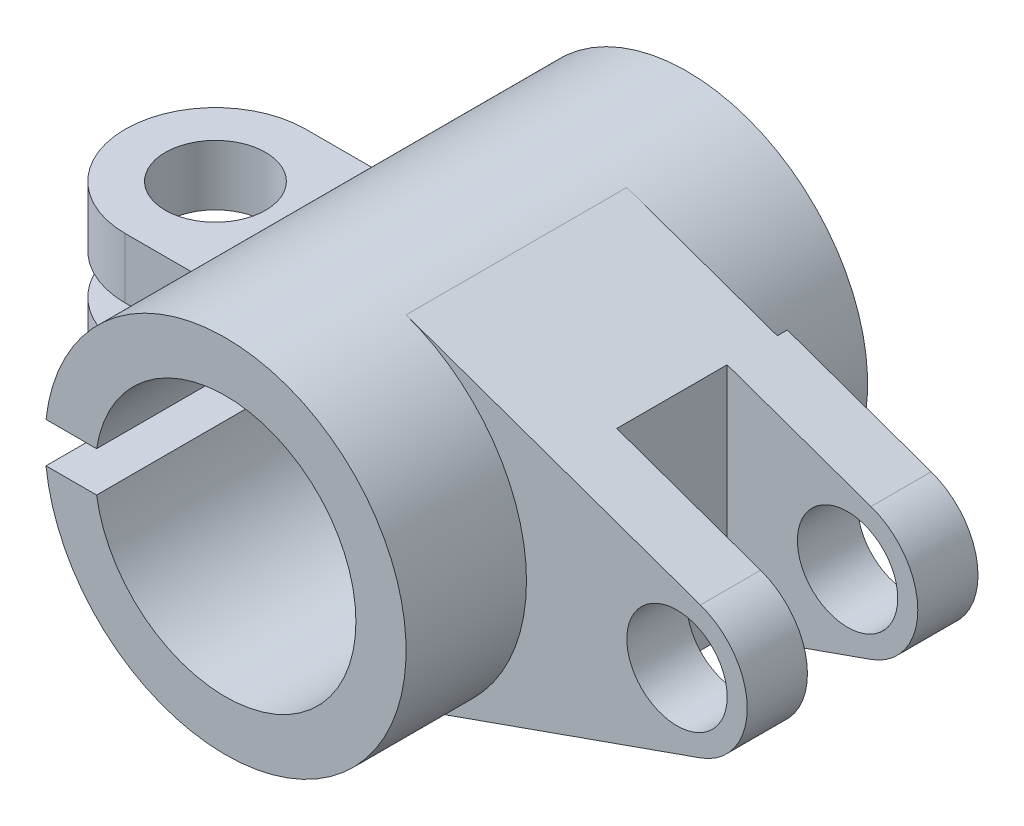
SolidWorks part; units mm, degrees
ref_plane "Front Plane" through (0, 0, 0) normal (0, 0, 1) x (1, 0, 0)
ref_plane "Top Plane" through (0, 0, 0) normal (0, 1, 0) x (1, 0, 0)
ref_plane "Right Plane" through (0, 0, 0) normal (1, 0, 0) x (0, 0, -1)
sketch "Sketch1" plane through (0, 0, 0) normal (0, 0, 1) x (1, 0, 0)
  line L0 (-16.1245, 8) -> (-33, 8)
  line L1 (-33, 8) -> (-33, 2)
  line L2 (0, 0) -> (-50000, 0) construction
  line L3 (0, 0) -> (0, -50000) construction
  line L4 (-33, 2) -> (-12.8452, 2)
  line L5 (-33, -8) -> (-33, -2)
  line L6 (-16.1245, -8) -> (-33, -8)
  line L7 (-33, -2) -> (-12.8452, -2)
  line L8 (6, 16.9706) -> (35.3333, 6.5997)
  line L9 (6, -16.9706) -> (35.3333, -6.5997)
  line L10 (21, 11.6673) -> (21, -11.6673)
  arc A0 (-12.8452, -2) -> (-12.8452, 2) centre (0, 0) ccw
  arc A1 (-17.8885, -2) -> (-17.8885, 2) centre (0, 0) ccw
  circle A2 centre (33, 0) radius 5
  arc A3 (35.3333, -6.5997) -> (35.3333, 6.5997) centre (33, 0) ccw
  dimension "D1" = 26
  dimension "D2" = 36
  dimension "D6" = 10
  dimension "D7" = 14
  dimension "D8" = 12
  dimension "D3" = 6
  dimension "D4" = 4
  dimension "D5" = 33
  dimension "D9" = 33
extrude "Boss-Extrude1" add sketch "Sketch1" along normal mid plane 46 contours A1 L4 A0 L7 region at (-6.5724, 16.2099, 0)
extrude "Boss-Extrude2" add sketch "Sketch1<3>" along normal mid plane 22 contours A1 L9 L10 L8 region at (13.3763, 13.9691, 0)
sketch "Sketch1<3>" plane through (0, 0, 0) normal (0, 0, 1) x (1, 0, 0) same geometry as "Sketch1"
extrude "Boss-Extrude3" add sketch "Sketch1<4>" along normal blind 6 from offset 5 contours L9 A3 L8 L10 A2 region at (27.5339, 0, 0)
sketch "Sketch1<4>" plane through (0, 0, 0) normal (0, 0, 1) x (1, 0, 0) same geometry as "Sketch1"
extrude "Boss-Extrude4" add sketch "Sketch1<5>" against normal blind 6 from offset 6 contours L9 A3 L8 L10 A2 region at (27.5339, 0, 0) offset against normal yes
sketch "Sketch1<5>" plane through (0, 0, 0) normal (0, 0, 1) x (1, 0, 0) same geometry as "Sketch1"
extrude "Boss-Extrude5" add sketch "Sketch1<6>" along normal mid plane 18 contours A1 L0 L1 L4 | A1 L7 L5 L6 region at (-25.0902, 5.0554, 0) region at (-25.0902, -5.0554, 0)
sketch "Sketch1<6>" plane through (0, 0, 0) normal (0, 0, 1) x (1, 0, 0) same geometry as "Sketch1"
fillet "Fillet1" 2 edges at (-33, 5, -9) (-33, 5, 9) type full round first side face at (-25.0689, 5.0193, -9) second side face at (-25.0689, 5.0193, 9) middle face at (-33, 5, 0)
fillet "Fillet2" 2 edges at (-33, -5, 9) (-33, -5, -9) type full round first side face at (-25.0689, -5.0193, 9) second side face at (-25.0689, -5.0193, -9) middle face at (-33, -5, 0)
hole_wizard "Ø10.0mm Dowel Hole1" positions "3DSketch1" profile "Sketch2" hole size "Ø10.0" standard "AS" end condition through all
sketch3d "3DSketch1"
  line L0 (-24, 8, 0) -> (-24, 2, 0) construction
  point P0 (-24, 8, 0)
sketch "Sketch2" plane through (-24, 8, 0) normal (1, 0, 0) x (0, 0, 1)
  line L0 (0, 0) -> (0, 26)
  line L1 (0, 26) -> (5, 26)
  line L2 (5, 26) -> (5, 0)
  line L5 (5, 0) -> (0, 0)
  line L11 (0, -6.35) -> (0, 107.95) construction
  dimension "Thru Hole Dia." = 10
  dimension "Thru Hole Depth" = 26
